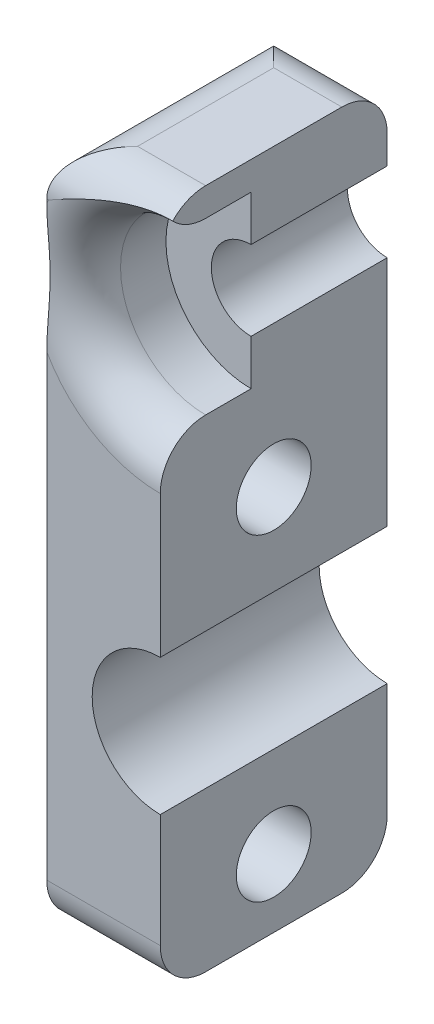
SolidWorks part; units mm, degrees
ref_plane "Front Plane" through (0, 0, 0) normal (0, 0, 1) x (1, 0, 0)
ref_plane "Top Plane" through (0, 0, 0) normal (0, 1, 0) x (1, 0, 0)
ref_plane "Right Plane" through (0, 0, 0) normal (1, 0, 0) x (0, 0, -1)
sketch "草圖1" plane through (0, 0, 0) normal (0, 0, 1) x (1, 0, 0)
  line L1 (5, -10) -> (-5, -10)
  line L2 (5, -10) -> (5, 10)
  line L3 (5, 10) -> (-5, 10)
  line L4 (-5, -10) -> (-5, 10)
  line L5 (5, -10) -> (-5, 10) construction
  line L6 (5, 10) -> (-5, -10) construction
  circle A0 centre (0, 0) radius 3
  point P0 (0, 0)
  dimension "D3" = 6
  dimension "D1" = 10
  dimension "D2" = 20
extrude "填料-伸長1" add sketch "草圖1" along normal blind 10
sketch "草圖2" plane through (-5, 0, 0) normal (-1, 0, 0) x (0, 0, 1)
  line L0 (0, 10) -> (0, -10) construction
  line L1 (10, 10) -> (0, 10) construction
  line L2 (10, -10) -> (0, -10) construction
  circle A0 centre (5, 7) radius 1.65
  circle A1 centre (5, -7) radius 1.65
  dimension "D1" = 3.3
  dimension "D2" = 5
  dimension "D3" = 3
  dimension "D4" = 3
extrude "除料-伸長1" cut sketch "草圖2" against normal through all
sketch "草圖3" plane through (0, 0, 10) normal (0, 0, 1) x (1, 0, 0)
  line L0 (5, 10) -> (-5, 10) construction
  line L1 (0, 10) -> (12.8527, 10)
  line L2 (0, 10) -> (0, -10.2796)
  line L3 (0, -10.2796) -> (12.8527, -10.2796)
  line L4 (12.8527, 10) -> (12.8527, -10.2796)
extrude "除料-伸長2" cut sketch "草圖3" against normal through all
sketch "草圖5" plane through (0, 0, 10) normal (0, 0, 1) x (1, 0, 0)
  line L0 (0, 10) -> (0, 13.25)
  line L1 (-5, 10) -> (0, 10)
  line L2 (-5, 10) -> (-5, 20)
  line L3 (-5, 20) -> (0, 20)
  line L5 (0, 16.75) -> (0, 20)
  line L6 (0, 10) -> (0, 3) construction
  arc A0 (0, 16.75) -> (0, 13.25) centre (0, 15) ccw
  dimension "D2" = 3.5
  dimension "D3" = 5
  dimension "D1" = 10
extrude "填料-伸長2" add sketch "草圖5" against normal through all
fillet "圓角1" radius 2 5 edges at (-2.5, 20, 10) (-2.5, 20, 0) (-2.5, -10, 0) (-2.5, -10, 10) (-5, 20, 5)
sketch "草圖6" plane through (0, 0, 10) normal (0, 0, 1) x (1, 0, 0)
  circle A0 centre (0, 15) radius 3.75
  dimension "D1" = 7.5
extrude "除料-伸長3" cut sketch "草圖6" against normal blind 4
fillet "圓角2" radius 2 1 edges at (-3.5576, 13.8141, 10)
